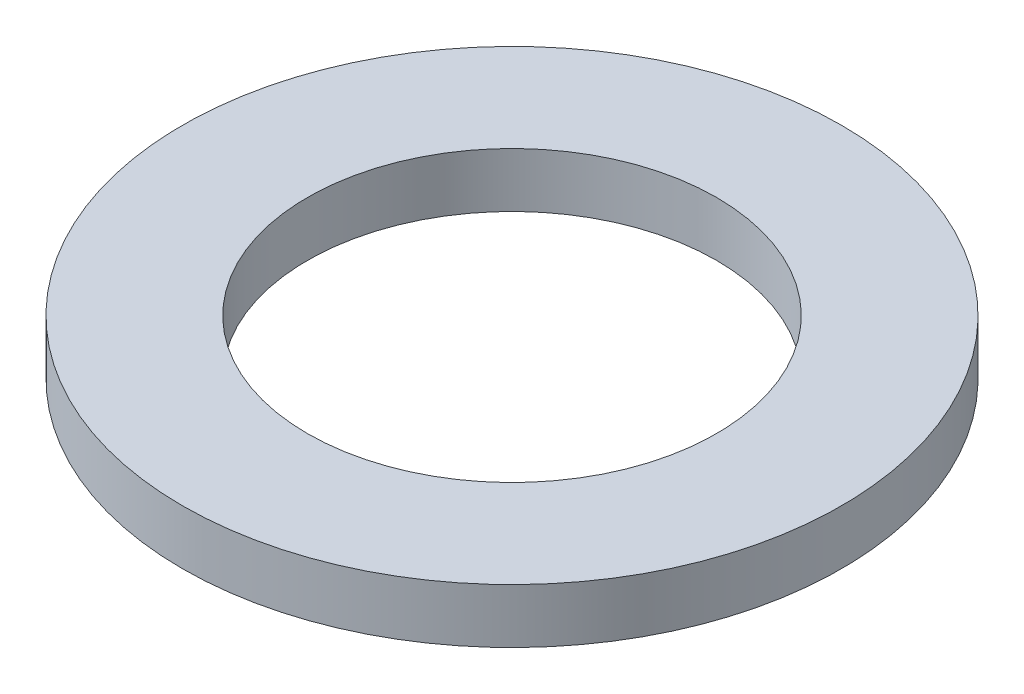
SolidWorks part; units mm, degrees
ref_plane "Front Plane" through (0, 0, 0) normal (0, 0, 1) x (1, 0, 0)
ref_plane "Top Plane" through (0, 0, 0) normal (0, 1, 0) x (1, 0, 0)
ref_plane "Right Plane" through (0, 0, 0) normal (1, 0, 0) x (0, 0, -1)
sketch "Sketch1" plane through (0, 0, 0) normal (0, 1, 0) x (1, 0, 0)
  circle A0 centre (0, 0) radius 72.5
  dimension "FLANGE_OD" = 145
extrude "Boss-Extrude1" add sketch "Sketch1" along normal blind 12
sketch "Sketch2" plane through (0, 0, 0) normal (0, 1, 0) x (1, 0, 0)
  circle A0 centre (0, 0) radius 45
  dimension "BORE_D" = 90
extrude "Cut-Extrude1" cut sketch "Sketch2" along normal through all
sketch "Sketch3" plane through (0, 12, 0) normal (0, 1, 0) x (1, 0, 0)
  circle A0 centre (0, 0) radius 29.6532 construction
  circle A1 centre (-29.6532, 0) radius 4.5662
  dimension "BOLT_D" = 9.1324
  dimension "BOLT_PCD" = 59.3065
extrude "Cut-Extrude2" cut sketch "Sketch3" against normal blind 10.3631 rebuild error yes
pattern_circular "CirPattern1" count 5 over 360 rebuild error yes
